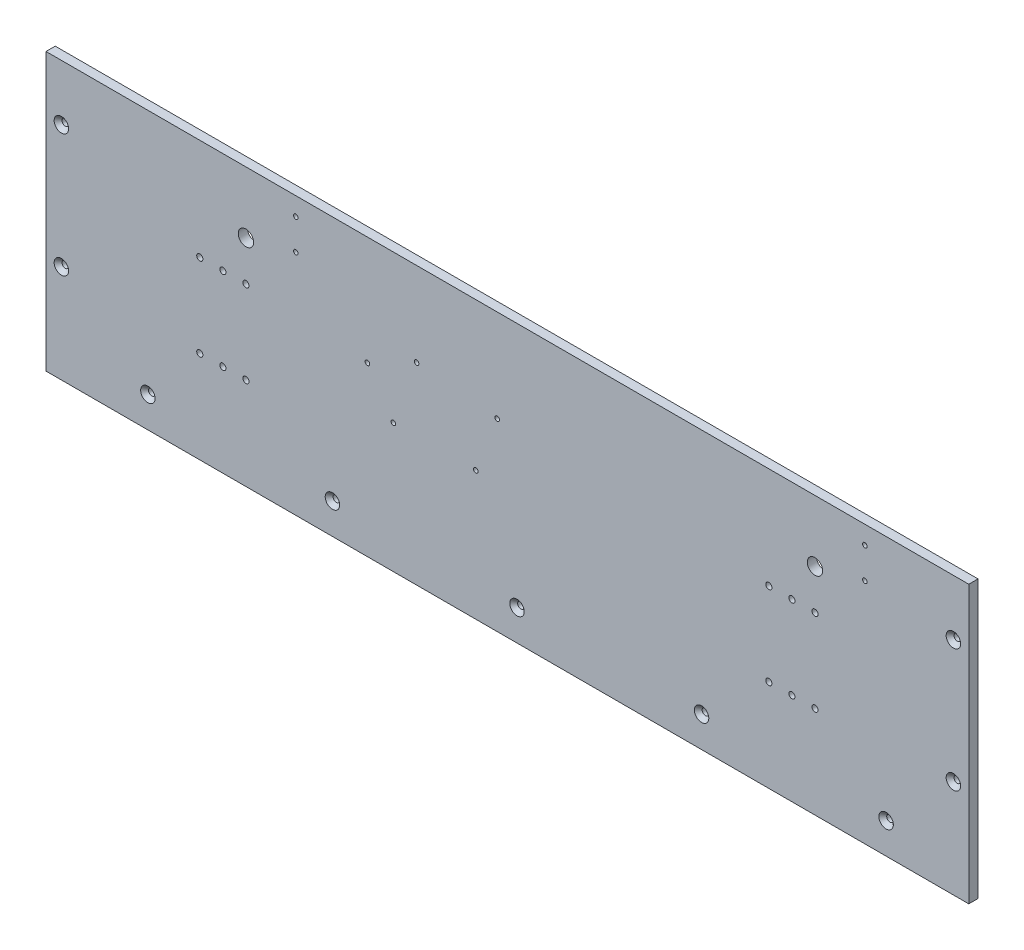
SolidWorks part; units mm, degrees
ref_plane "Płaszczyzna przednia" through (0, 0, 0) normal (0, 0, 1) x (1, 0, 0)
ref_plane "Płaszczyzna górna" through (0, 0, 0) normal (0, 1, 0) x (1, 0, 0)
ref_plane "Płaszczyzna prawa" through (0, 0, 0) normal (1, 0, 0) x (0, 0, -1)
sketch "Sketch1" plane through (0, 0, 0) normal (0, 0, 1) x (1, 0, 0)
  line L1 (0, 0) -> (600, 0)
  line L2 (0, 0) -> (0, 180)
  line L3 (0, 180) -> (600, 180)
  line L4 (600, 0) -> (600, 180)
  line L5 (0, 0) -> (600, 180) construction
  line L6 (0, 180) -> (600, 0) construction
  point P4 (300, 90)
  dimension "D1" = 600
  dimension "D2" = 180
extrude "Boss-Extrude1" add sketch "Sketch1" along normal blind 6
hole_wizard "CSK for M4 Flat Head Machine Screw1" positions "Sketch2" profile "Sketch3" countersink size "M4" standard "ANSI Metric" end condition through all
sketch "Sketch2" plane through (0, 0, 6) normal (0, 0, 1) x (1, 0, 0)
  line L0 (600, 0) -> (600, 180) construction
  line L1 (0, 0) -> (600, 0) construction
  point P0 (546.25, 20)
  point P2 (590, 63.75)
  point P13 (426.25, 20)
  point P14 (306.25, 20)
  point P15 (186.25, 20)
  point P16 (66.25, 20)
  point P21 (10, 63.75)
  point P28 (590, 143.75)
  point P29 (10, 143.75)
  dimension "D1" = 53.75
  dimension "D2" = 63.75
  dimension "D3" = 10
  dimension "D4" = 20
  dimension "D5" = 5
  dimension "D6" = 2
  dimension "D7" = 2
sketch "Sketch3" plane through (546.25, 20, 6) normal (1, 0, 0) x (0, -1, 0)
  line L0 (0, 0) -> (0, 6)
  line L1 (0, 6) -> (2.15, 6)
  line L2 (2.15, 6) -> (2.15, 2.55)
  line L3 (2.15, 2.55) -> (4.7, 0)
  line L5 (4.7, 0) -> (0, 0)
  line L6 (-2.15, 2.55) -> (-4.7, 0) construction
  line L11 (0, -6.35) -> (0, 107.95) construction
  dimension "Thru Hole Dia." = 4.3
  dimension "Thru Hole Depth" = 6
  dimension "Near C'Sink Dia." = 9.4
  dimension "Near C'Sink Angle" = 90
hole_wizard "Ø4.0mm Dowel Hole1" positions "Sketch4" profile "Sketch5" hole size "Ø4.0" standard "ANSI Metric" end condition through all
sketch "Sketch4" plane through (0, 0, 6) normal (0, 0, 1) x (1, 0, 0)
  line L0 (600, 0) -> (600, 180) construction
  line L1 (0, 0) -> (600, 0) construction
  line L2 (300, 0) -> (300, 180) construction
  line L3 (600, 180) -> (0, 180) construction
  point P0 (500, 60)
  point P9 (485, 60)
  point P10 (470, 60)
  point P11 (485, 114)
  point P12 (470, 114)
  point P13 (500, 114)
  point P24 (130, 114)
  point P25 (115, 114)
  point P26 (100, 114)
  point P27 (130, 60)
  point P28 (115, 60)
  point P29 (100, 60)
  dimension "D3" = 100
  dimension "D4" = 60
  dimension "D1" = 3
  dimension "D2" = 2
sketch "Sketch5" plane through (500, 60, 6) normal (1, 0, 0) x (0, -1, 0)
  line L0 (0, 0) -> (0, 6)
  line L1 (0, 6) -> (2, 6)
  line L2 (2, 6) -> (2, 0)
  line L5 (2, 0) -> (0, 0)
  line L11 (0, -6.35) -> (0, 107.95) construction
  dimension "Thru Hole Dia." = 4
  dimension "Thru Hole Depth" = 6
hole_wizard "Ø3.0mm Dowel Hole1" positions "Sketch6" profile "Sketch7" hole size "Ø3.0" standard "ANSI Metric" end condition through all
sketch "Sketch6" plane through (0, 0, 6) normal (0, 0, 1) x (1, 0, 0)
  line L0 (0, 0) -> (600, 0) construction
  line L2 (600, 0) -> (600, 180) construction
  line L3 (300, 0) -> (300, 181.4009) construction
  line L5 (600, 0) -> (600, 552) construction
  line L6 (0, 180) -> (0, 0) construction
  point P0 (532.43, 148.2)
  point P2 (532.43, 168.2)
  point P23 (162.43, 148.2)
  point P25 (162.43, 168.2)
  dimension "D1" = 20
  dimension "D2" = 148.2
  dimension "D3" = 67.57
  dimension "D4" = 300
  dimension "D5" = 162.43
  dimension "D6" = 20
  dimension "D7" = 148.2
sketch "Sketch7" plane through (532.43, 148.2, 6) normal (1, 0, 0) x (0, -1, 0)
  line L0 (0, 0) -> (0, 6)
  line L1 (0, 6) -> (1.5, 6)
  line L2 (1.5, 6) -> (1.5, 0)
  line L5 (1.5, 0) -> (0, 0)
  line L11 (0, -6.35) -> (0, 107.95) construction
  dimension "Thru Hole Dia." = 3
  dimension "Thru Hole Depth" = 6
sketch "Sketch8" plane through (0, 0, 6) normal (0, 0, 1) x (1, 0, 0)
  line L0 (600, 0) -> (600, 180) construction
  line L1 (0, 0) -> (600, 0) construction
  line L2 (0, 180) -> (0, 0) construction
  circle A0 centre (500, 140) radius 5
  circle A1 centre (130, 140) radius 5
  dimension "D1" = 10
  dimension "D2" = 100
  dimension "D3" = 140
  dimension "D4" = 10
  dimension "D5" = 140
  dimension "130" = 130
extrude "Cut-Extrude1" cut sketch "Sketch8" against normal blind 10
hole_wizard "Ø3.0mm Dowel Hole2" positions "Sketch9" profile "Sketch10" hole size "Ø3.0" standard "ANSI Metric" end condition through all
sketch "Sketch9" plane through (0, 0, 6) normal (0, 0, 1) x (1, 0, 0)
  point P0 (279.4381, 83.8378)
  point P3 (225.8441, 83.8378)
  point P6 (209.0041, 109.1618)
  point P9 (240.9571, 125.3158)
  point P12 (293.4081, 119.9058)
sketch "Sketch10" plane through (279.4381, 83.8378, 6) normal (1, 0, 0) x (0, -1, 0)
  line L0 (0, 0) -> (0, 6)
  line L1 (0, 6) -> (1.5, 6)
  line L2 (1.5, 6) -> (1.5, 0)
  line L5 (1.5, 0) -> (0, 0)
  line L11 (0, -6.35) -> (0, 107.95) construction
  dimension "Thru Hole Dia." = 3
  dimension "Thru Hole Depth" = 6
